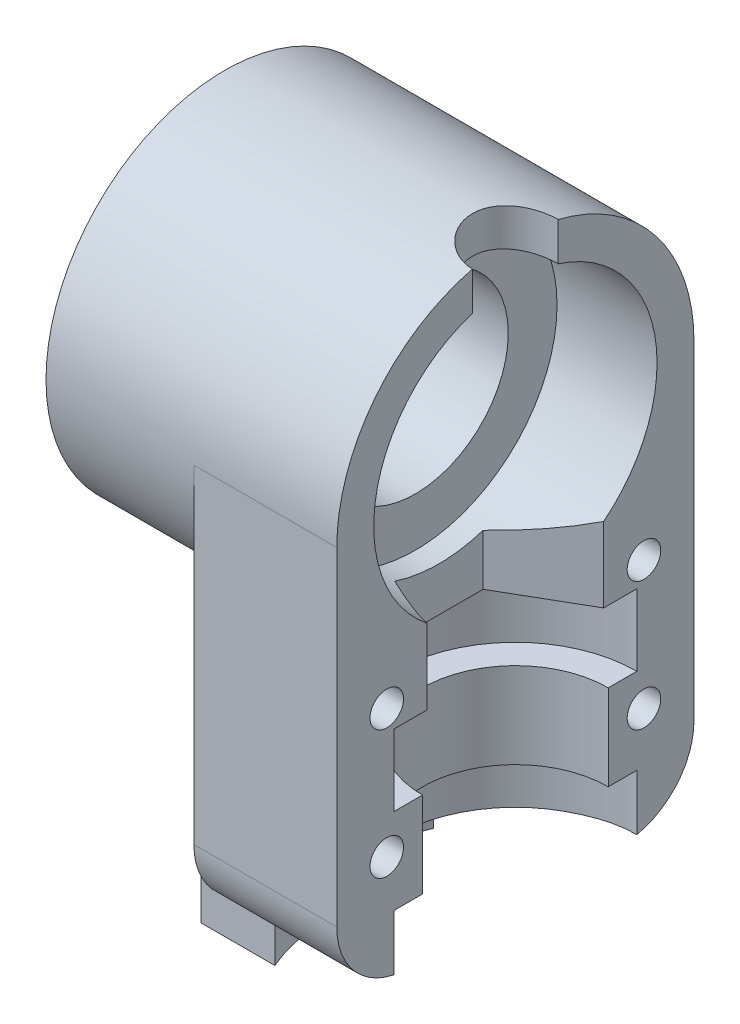
SolidWorks part; units mm, degrees
material "ABS"
ref_plane "Alzado" through (0, 0, 0) normal (0, 0, 1) x (1, 0, 0)
ref_plane "Planta" through (0, 0, 0) normal (0, 1, 0) x (1, 0, 0)
ref_plane "Vista lateral" through (0, 0, 0) normal (1, 0, 0) x (0, 0, -1)
sketch "Croquis1" plane through (0, 0, 0) normal (0, 1, 0) x (1, 0, 0)
  line L1 (0, 0) -> (-10, 0)
  line L2 (0, 0) -> (0, 25)
  line L3 (0, 25) -> (-10, 25)
  line L4 (-10, 0) -> (-10, 25)
  dimension "D1" = 25
  dimension "D2" = 10
extrude "Saliente-Extruir1" add sketch "Croquis1" along normal blind 28
sketch "Croquis2" plane through (0, 0, 0) normal (1, 0, 0) x (0, 0, -1)
  line L0 (0, 28) -> (25, 28) construction
  circle A0 centre (12.5, 28) radius 12.5
  dimension "D1" = 25
extrude "Saliente-Extruir2" add sketch "Croquis2" against normal blind 12
sketch "Croquis3" plane through (0, 0, 0) normal (1, 0, 0) x (0, 0, -1)
  line L2 (12.5, 0.5) -> (20.5, 0.5) construction
  line L3 (20.5, 0.5) -> (20.5, 3.5) construction
  line L4 (20.5, 3.5) -> (18.5, 3.5) construction
  line L5 (18.5, 3.5) -> (18.5, 10.5) construction
  line L6 (18.5, 10.5) -> (20.5, 10.5) construction
  line L7 (20.5, 10.5) -> (20.5, 14.5) construction
  line L8 (20.5, 14.5) -> (12.5, 14.5) construction
  line L9 (21, 0.5) -> (21, 4)
  line L10 (21, 4) -> (19, 4)
  line L11 (19, 4) -> (19, 10)
  line L12 (19, 10) -> (21, 10)
  line L13 (21, 10) -> (21, 15)
  line L14 (21, 15) -> (15.5, 15)
  line L15 (0, 0) -> (25, 0) construction
  line L16 (12.5, 0) -> (12.5, 41)
  line L17 (12.5, 0) -> (21, 0)
  line L18 (21, 0) -> (21, 0.5)
  line L20 (21, 15) -> (12.5, 15) construction
  line L21 (12.5, 41) -> (15.5, 41)
  line L22 (15.5, 41) -> (15.5, 15)
  point P20 (12.5, 0)
  dimension "D1" = 8
  dimension "D2" = 3
  dimension "D3" = 6
  dimension "D4" = 7
  dimension "D5" = 4
  dimension "D6" = 0.5
  dimension "D7" = 0.5
  dimension "D8" = 3
  dimension "D9" = 41
revolve "Cortar-Revolución1" cut sketch "Croquis3" angle 360 about L16
fillet "Redondeo1" radius 5 2 edges at (-5, 0, -25) (-5, 0, 0)
sketch "Croquis4" plane through (0, 15, 0) normal (0, -1, 0) x (1, 0, 0)
  line L0 (0, -15.5) -> (0, -21) construction
  line L1 (0, -18.2735) -> (5, -15.3868) construction
  line L2 (5, -15.3868) -> (5, -9.6132) construction
  line L3 (5, -9.6132) -> (0, -6.7265) construction
  line L4 (0, -6.7265) -> (-5, -9.6132) construction
  line L5 (-5, -9.6132) -> (-5, -15.3868) construction
  line L6 (-5, -15.3868) -> (0, -18.2735) construction
  line L7 (0, -18.6776) -> (5.35, -15.5888)
  line L8 (5.35, -15.5888) -> (5.35, -9.4112)
  line L9 (5.35, -9.4112) -> (0, -6.3224)
  line L10 (0, -6.3224) -> (-5.35, -9.4112)
  line L11 (-5.35, -9.4112) -> (-5.35, -15.5888)
  line L12 (-5.35, -15.5888) -> (0, -18.6776)
  circle A0 centre (0, -12.5) radius 5 construction
  dimension "D1" = 10
  dimension "D2" = 0.35
extrude "Cortar-Extruir1" cut sketch "Croquis4" against normal blind 13
sketch "Croquis5" plane through (0, 0, 0) normal (1, 0, 0) x (0, 0, -1)
  circle A0 centre (12.5, 28) radius 9.915
  dimension "D1" = 19.83
extrude "Cortar-Extruir2" cut sketch "Croquis5" against normal offset from surface (7 mm away) 5 up to face at (-12, 28, -25)
sketch "Croquis8" plane through (0, 0, 0) normal (1, 0, 0) x (0, 0, -1)
  line L1 (0, 28) -> (0, 5) construction
  line L2 (4, 15) -> (6.3224, 15) construction
  line L3 (25, 28) -> (25, 5) construction
  circle A0 centre (21.5, 16.5) radius 1.175
  circle A1 centre (3.5, 16.5) radius 1.175
  circle A2 centre (3.5, 7.5) radius 1.175
  circle A3 centre (21.5, 7.5) radius 1.175
  dimension "D1" = 1.5
  dimension "D2" = 2.35
  dimension "D3" = 3.5
  dimension "D5" = 9
  dimension "D6" = 3.5
extrude "Cortar-Extruir5" cut sketch "Croquis8" against normal through all
ref_plane "Plano1" through (0, 0, -12.5) normal (0, 0, 1) x (1, 0, 0)
sketch "Croquis10" plane through (0, 0, -12.5) normal (0, 0, 1) x (1, 0, 0)
  line L0 (-10, 28) -> (-10, 5) construction
  line L1 (-10, 8) -> (-17, 8)
  line L2 (-10, 8) -> (-10, -7)
  line L3 (-10, -7) -> (-17, -7)
  line L4 (-17, 8) -> (-17, -7)
  line L5 (-4, 0) -> (-10, 0) construction
  point P6 (-13.5, 8)
  dimension "D1" = 8
  dimension "D2" = 15
  dimension "D3" = 7
extrude "Saliente-Extruir3" add sketch "Croquis10" along normal mid plane 10
sketch "Croquis11" plane through (0, -7, 0) normal (0, -1, 0) x (1, 0, 0)
  line L4 (-17, -17.5) -> (-10, -17.5)
  line L5 (-10, -17.5) -> (-10, -7.5)
  line L6 (-10, -7.5) -> (-17, -7.5)
  line L7 (-17, -7.5) -> (-17, -17.5)
  line L8 (-10.7435, -17.5) -> (-10, -17.5)
  line L9 (-10, -17.5) -> (-10, -7.5)
  line L10 (-10, -7.5) -> (-10.7435, -7.5)
  arc A0 (-10.7435, -7.5) -> (-10.7435, -17.5) centre (0, -12.5) ccw
  arc A1 (0, -9.5) -> (0, -15.5) centre (0, -12.5) ccw construction
  dimension "D1" = 11.85
  dimension "D2" = 0
extrude "Cortar-Extruir6" cut sketch "Croquis11" against normal up to surface (7 mm away) up to face at (-8.75, 0, -12.5)
sketch "Croquis12" plane through (0, -7, 0) normal (0, -1, 0) x (1, 0, 0)
  line L0 (-12.35, -10.5693) -> (-15.5, -30.719) construction
  line L2 (12.35, -10.5693) -> (15.5, -30.719) construction
  line L3 (-17, -17.5) -> (-10.7435, -17.5)
  line L4 (-10.7435, -7.5) -> (-17, -7.5)
  line L5 (-17, -7.5) -> (-17, -17.5)
  line L6 (-13.7877, -17.5) -> (-10.7435, -17.5)
  line L7 (-10.7435, -7.5) -> (-11.8373, -7.5)
  line L9 (15.5, -30.719) -> (-15.5, -30.719) construction
  line L10 (11.135, -6.8201) -> (-11.135, -6.8201) construction
  line L11 (-12.6958, -10.5153) -> (-13.7877, -17.5)
  line L15 (-12.6958, -10.5153) -> (-15.909, -31.069) construction
  line L16 (11.3473, -6.4701) -> (-11.3473, -6.4701) construction
  line L17 (12.6958, -10.5153) -> (15.909, -31.069) construction
  line L18 (15.909, -31.069) -> (-15.909, -31.069) construction
  arc A1 (12.35, -10.5693) -> (11.135, -6.8201) centre (0, -12.5) ccw construction
  arc A2 (-10.7435, -7.5) -> (-10.7435, -17.5) centre (0, -12.5) ccw
  arc A4 (-11.135, -6.8201) -> (-12.35, -10.5693) centre (0, -12.5) ccw construction
  arc A6 (-11.8373, -7.5) -> (-12.6958, -10.5153) centre (0, -12.5) ccw
  arc A7 (-11.3473, -6.4701) -> (-12.6958, -10.5153) centre (0, -12.5) ccw construction
  arc A8 (12.6958, -10.5153) -> (11.3473, -6.4701) centre (0, -12.5) ccw construction
  arc A10 (-10.7435, -7.5) -> (-10.7435, -17.5) centre (0, -12.5) ccw
  point P5 (0, -30.719)
  dimension "D1" = 0
  dimension "D2" = 25
  dimension "D3" = 31
  dimension "D4" = 24.7
  dimension "D5" = 22.27
  dimension "D6" = 0.35
extrude "Cortar-Extruir7" cut sketch "Croquis12" against normal blind 3.85
chamfer "Chaflán1" distance 4.3 angle 50 1 edges at (-17, 8, -12.5) first distance on face at (-13.5, 8, -12.5)
fillet "Redondeo2" radius 1 2 edges at (-12.3589, -3.15, -8.9814) (-13.2418, -3.15, -14.0076)
sketch "Croquis13" plane through (-10, 0, 0) normal (-1, 0, 0) x (0, 0, 1)
  line L0 (-21.5, 18.8309) -> (-23.5187, 17.6655)
  line L1 (-21.5, 18.6) -> (-23.3187, 17.55) construction
  line L2 (-23.3187, 17.55) -> (-23.3187, 15.45) construction
  line L3 (-23.3187, 15.45) -> (-21.5, 14.4) construction
  line L4 (-21.5, 14.4) -> (-19.6813, 15.45) construction
  line L5 (-19.6813, 15.45) -> (-19.6813, 17.55) construction
  line L6 (-19.6813, 17.55) -> (-21.5, 18.6) construction
  line L7 (-3.5, 18.6) -> (-5.3187, 17.55) construction
  line L8 (-5.3187, 17.55) -> (-5.3187, 15.45) construction
  line L9 (-5.3187, 15.45) -> (-3.5, 14.4) construction
  line L10 (-3.5, 14.4) -> (-1.6813, 15.45) construction
  line L11 (-1.6813, 15.45) -> (-1.6813, 17.55) construction
  line L12 (-1.6813, 17.55) -> (-3.5, 18.6) construction
  line L13 (-3.5, 9.6) -> (-5.3187, 8.55) construction
  line L14 (-5.3187, 8.55) -> (-5.3187, 6.45) construction
  line L15 (-5.3187, 6.45) -> (-3.5, 5.4) construction
  line L16 (-3.5, 5.4) -> (-1.6813, 6.45) construction
  line L17 (-1.6813, 6.45) -> (-1.6813, 8.55) construction
  line L18 (-1.6813, 8.55) -> (-3.5, 9.6) construction
  line L19 (-21.5, 9.6) -> (-23.3187, 8.55) construction
  line L20 (-23.3187, 8.55) -> (-23.3187, 6.45) construction
  line L21 (-23.3187, 6.45) -> (-21.5, 5.4) construction
  line L22 (-21.5, 5.4) -> (-19.6813, 6.45) construction
  line L23 (-19.6813, 6.45) -> (-19.6813, 8.55) construction
  line L24 (-19.6813, 8.55) -> (-21.5, 9.6) construction
  line L25 (-23.5187, 17.6655) -> (-23.5187, 15.3345)
  line L26 (-23.5187, 15.3345) -> (-21.5, 14.1691)
  line L27 (-21.5, 14.1691) -> (-19.4813, 15.3345)
  line L28 (-19.4813, 15.3345) -> (-19.4813, 17.6655)
  line L29 (-19.4813, 17.6655) -> (-21.5, 18.8309)
  line L30 (-3.5, 18.8309) -> (-5.5187, 17.6655)
  line L31 (-5.5187, 17.6655) -> (-5.5187, 15.3345)
  line L32 (-5.5187, 15.3345) -> (-3.5, 14.1691)
  line L33 (-3.5, 14.1691) -> (-1.4813, 15.3345)
  line L34 (-1.4813, 15.3345) -> (-1.4813, 17.6655)
  line L35 (-1.4813, 17.6655) -> (-3.5, 18.8309)
  line L36 (-3.5, 9.8309) -> (-5.5187, 8.6655)
  line L37 (-5.5187, 8.6655) -> (-5.5187, 6.3345)
  line L38 (-5.5187, 6.3345) -> (-3.5, 5.1691)
  line L39 (-3.5, 5.1691) -> (-1.4813, 6.3345)
  line L40 (-1.4813, 6.3345) -> (-1.4813, 8.6655)
  line L41 (-1.4813, 8.6655) -> (-3.5, 9.8309)
  line L42 (-21.5, 9.8309) -> (-23.5187, 8.6655)
  line L43 (-23.5187, 8.6655) -> (-23.5187, 6.3345)
  line L44 (-23.5187, 6.3345) -> (-21.5, 5.1691)
  line L45 (-21.5, 5.1691) -> (-19.4813, 6.3345)
  line L46 (-19.4813, 6.3345) -> (-19.4813, 8.6655)
  line L47 (-19.4813, 8.6655) -> (-21.5, 9.8309)
  circle A0 centre (-21.5, 16.5) radius 1.8187 construction
  circle A1 centre (-3.5, 16.5) radius 1.8187 construction
  circle A2 centre (-3.5, 7.5) radius 1.8187 construction
  circle A3 centre (-21.5, 7.5) radius 1.8187 construction
  circle A4 centre (-21.5, 16.5) radius 2.0187 construction
  circle A5 centre (-3.5, 16.5) radius 2.0187 construction
  circle A6 centre (-3.5, 7.5) radius 2.0187 construction
  circle A7 centre (-21.5, 7.5) radius 2.0187 construction
  dimension "D1" = 4.2
  dimension "D2" = 0.2
extrude "Cortar-Extruir8" cut sketch "Croquis13" against normal blind 4
fillet "Redondeo3" radius 3 2 edges at (-17, 2.8755, -12.5) (-12.7, 8, -12.5)
sketch "Croquis14" plane through (-12, 0, 0) normal (-1, 0, 0) x (0, 0, 1)
  circle A1 centre (-12.5, 28) radius 12.5
  circle A3 centre (-12.5, 28) radius 11 construction
  circle A4 centre (-12.5, 28) radius 11.25
  circle A5 centre (-12.5, 28) radius 12.5 construction
  circle M4 centre (-12.5, 28) radius 12.5
  dimension "D1" = 22
  dimension "D2" = 22.5
  dimension "D3" = 25
extrude "Saliente-Extruir4" add sketch "Croquis14" along normal blind 7.35 contours A4 M4 region at (-12, 28, -24.6464)
sketch "Croquis15" plane through (-19.35, 0, 0) normal (-1, 0, 0) x (0, 0, 1)
  circle A1 centre (-12.5, 28) radius 12.5
  circle A3 centre (-12.5, 28) radius 11.25 construction
  circle A4 centre (-12.5, 28) radius 11
  dimension "D1" = 22
  dimension "D2" = 22.5
  dimension "D3" = 25
  dimension "D4" = 12.5
  dimension "D5" = 28
extrude "Saliente-Extruir5" add sketch "Croquis15" along normal blind 1
chamfer "Chaflán2" distance 0.5 angle 45 1 edges at (-20.35, 28, -1.5)
chamfer "Chaflán3" distance 0.5 angle 45 1 edges at (-19.35, 28, -1.5)
sketch "Croquis16" plane through (-7, 0, 0) normal (1, 0, 0) x (0, 0, -1)
  circle A0 centre (12.5, 28) radius 6.5
  dimension "D1" = 13
extrude "Cortar-Extruir9" cut sketch "Croquis16" against normal through all
ref_axis "Eje1" through (-52.0134, 28, -12.5) along (1, 0, 0)
